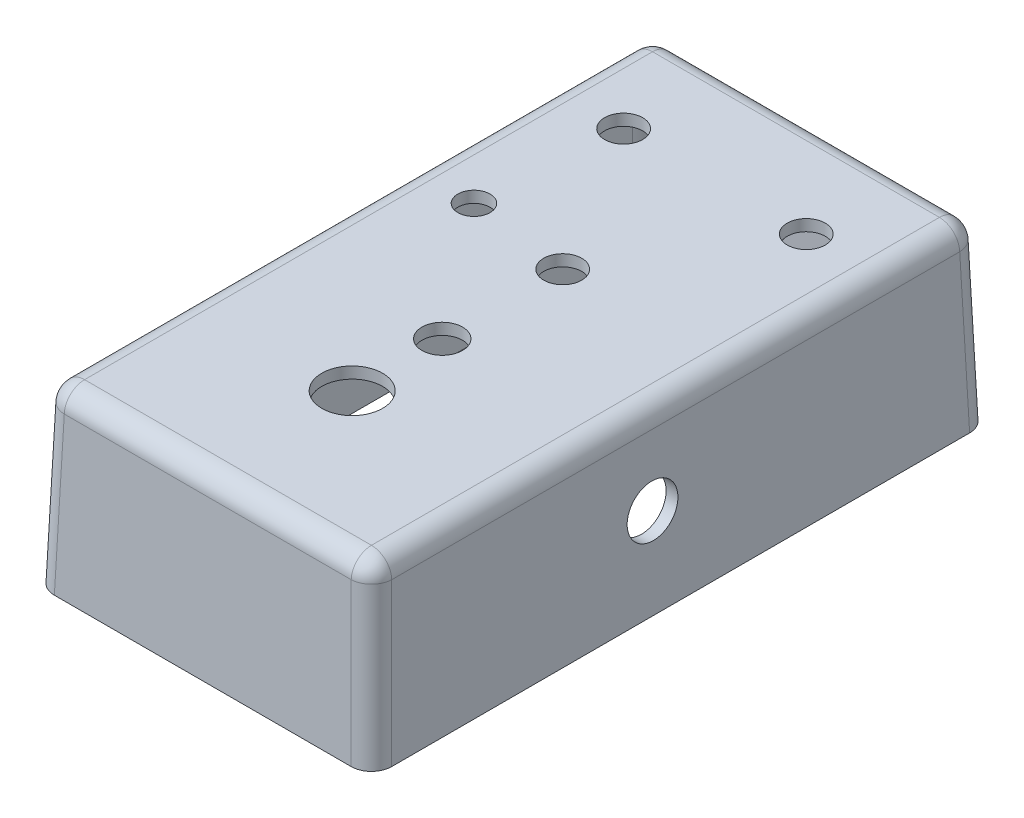
SolidWorks part; units mm, degrees
ref_plane "Front Plane" through (0, 0, 0) normal (0, 0, 1) x (1, 0, 0)
ref_plane "Top Plane" through (0, 0, 0) normal (0, 1, 0) x (1, 0, 0)
ref_plane "Right Plane" through (0, 0, 0) normal (1, 0, 0) x (0, 0, -1)
sketch "Sketch1" plane through (0, 0, 0) normal (0, 1, 0) x (1, 0, 0)
  line L1 (-33.25, -60.95) -> (33.25, -60.95)
  line L2 (-33.25, -60.95) -> (-33.25, 60.95)
  line L3 (-33.25, 60.95) -> (33.25, 60.95)
  line L4 (33.25, -60.95) -> (33.25, 60.95)
  line L5 (-33.25, -60.95) -> (33.25, 60.95) construction
  line L6 (-33.25, 60.95) -> (33.25, -60.95) construction
  point P0 (0, 0)
  dimension "D1" = 121.9
  dimension "D2" = 66.5
extrude "Box" add sketch "Sketch1" against normal blind 34.8
sketch "Sketch4" plane through (0, -34.8, 0) normal (0, -1, 0) x (1, 0, 0)
  line L9 (31, -58.7) -> (31, 58.7)
  line L10 (31, -58.7) -> (31, 58.7)
  line L11 (31, 58.7) -> (-31, 58.7)
  line L12 (31, 58.7) -> (-31, 58.7)
  line L17 (-31, 58.7) -> (-31, -58.7)
  line L18 (-31, 58.7) -> (-31, -58.7)
  line L19 (-31, -58.7) -> (31, -58.7)
  line L20 (-31, -58.7) -> (31, -58.7)
  dimension "D1" = 2.25
extrude "Hollow" cut sketch "Sketch4" against normal blind 32.55
chamfer "Side wall draft" distance 34.8 distance2 1.1 8 edges at (0, 0, 60.95) (-33.25, 0, 0) (0, 0, -60.95) (33.25, 0, 0) (-31, -2.25, 0) (0, -2.25, 58.7) (31, -2.25, 0) (0, -2.25, -58.7) first distance on face at (0, -17.4, 60.95) first distance on face at (-33.25, -17.4, 0) first distance on face at (0, -17.4, -60.95) first distance on face at (33.25, -17.4, 0) first distance on face at (-31, -18.525, 0) first distance on face at (0, -18.525, 58.7) first distance on face at (31, -18.525, 0) first distance on face at (0, -18.525, -58.7)
sketch "Sketch6" plane through (32.1179, 1.0152, 0) normal (0.9995, 0.0316, 0) x (0, 0, -1)
  line L0 (-59.85, -1.0157) -> (59.85, -1.0157) construction
  line L3 (0, -1.0157) -> (0, -39.1089) construction
  circle A0 centre (-5, -18.4157) radius 5
  dimension "D3" = 10
  dimension "D1" = 17.4
  dimension "D2" = 5
fillet "Corner rounding" radius 4 16 edges at (-32.7, -17.4, 60.4) (-32.7, -17.4, -60.4) (32.7, -17.4, -60.4) (32.7, -17.4, 60.4) (-30.4144, -18.525, -58.1144) (30.4144, -18.525, 58.1144) (30.4144, -18.525, -58.1144) (-30.4144, -18.525, 58.1144) (0, 0, -59.85) (32.15, 0, 0) (0, 0, 59.85) (-32.15, 0, 0) (29.9, -2.25, 0) (0, -2.25, -57.6) (-29.9, -2.25, 0) (0, -2.25, 57.6)
sketch "Sketch2" plane through (0, 0, 0) normal (0, 1, 0) x (1, 0, 0)
  circle A1 centre (-18, 40) radius 3.75
  circle A2 centre (0, -13.75) radius 4
  circle A3 centre (0, -31.5) radius 6
  circle A4 centre (-20, 12.5) radius 3.175
  circle A5 centre (18, 40) radius 3.75
  circle A8 centre (0, 10) radius 3.75
  dimension "D3" = 6.35
  dimension "D4" = 7.5
  dimension "D5" = 8
  dimension "D6" = 12
  dimension "D12" = 7.5
  dimension "D1" = 18
  dimension "D2" = 40
  dimension "D7" = 13.75
  dimension "D8" = 31.5
  dimension "D11" = 12.5
  dimension "D13" = 20
  dimension "D14" = 10
  dimension "D9" = 2
  dimension "D10" = 1
extrude "Top side cut" cut sketch "Sketch2" against normal blind 22.5
extrude "Input Jack" cut sketch "Sketch6" against normal blind 10
sketch "Sketch7" plane through (-32.1179, 1.0152, 0) normal (-0.9995, 0.0316, 0) x (0, 0, 1)
  line L0 (0, -4.8913) -> (0, -35.8331) construction
  line L1 (55.9744, -4.8913) -> (-55.9744, -4.8913) construction
  line L2 (-56.952, -35.8331) -> (56.952, -35.8331) construction
  line L3 (-55.9744, -0.8933) -> (55.9744, -0.8933) construction
  circle A0 centre (5, -18.2933) radius 5
  dimension "D1" = 10
  dimension "D2" = 17.4
  dimension "D3" = 5
extrude "Output Jack" cut sketch "Sketch7" against normal blind 10
equation "\"Height\"= 34.8"
equation "\"wall\"= 2.25"
equation "\"D1@Box\"=\"Height\""
equation "\"Holewidth\"=18"
equation "\"D1@Sketch2\"=\"Holewidth\""
equation "\"PotHole\"=7.5"
equation "\"D4@Sketch2\"=\"PotHole\""
equation "\"D12@Sketch2\"=\"PotHole\""
equation "\"D1@Hollow\"=\"Height\" - \"wall\""
equation "\"D1@Side wall draft\"=\"Height\""
equation "\"Jackoffset\"=5"
equation "\"D2@Sketch6\"=\"Jackoffset\""
equation "\"jackfromtop\"= \"Height\" / 2"
equation "\"D1@Sketch6\"=\"jackfromtop\""
equation "\"D3@Sketch7\"=\"Jackoffset\""
equation "\"D2@Sketch7\"=\"jackfromtop\""
